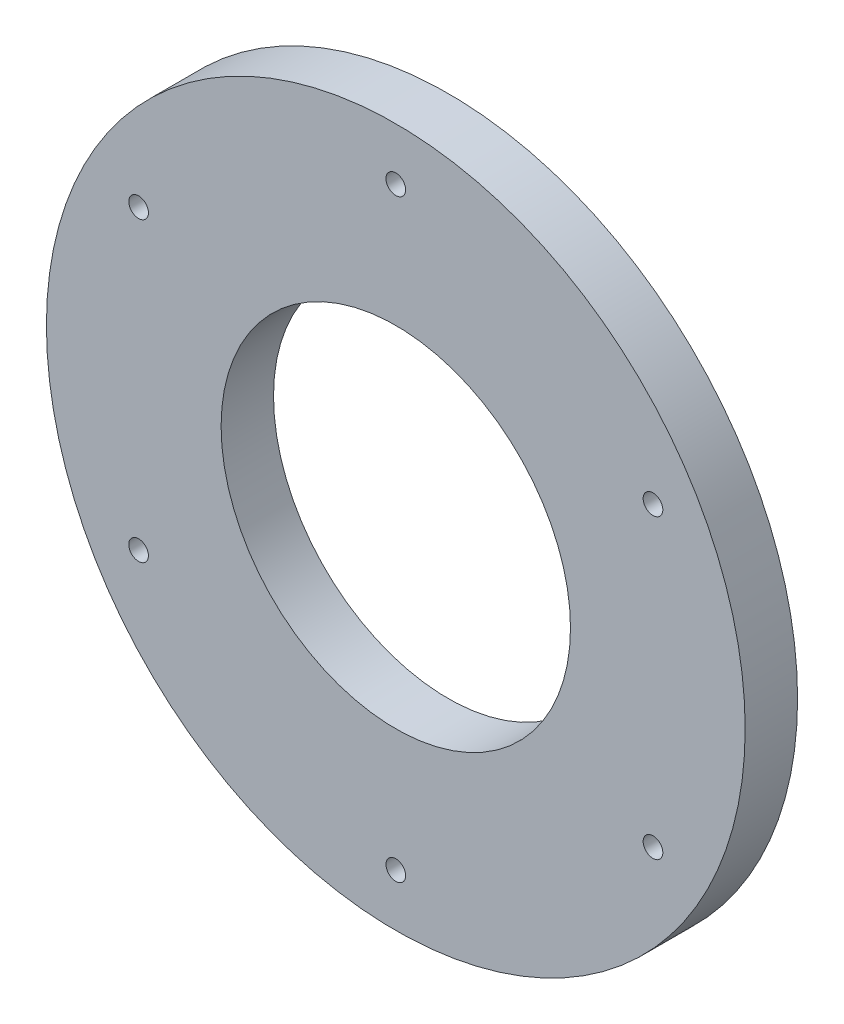
SolidWorks part; units mm, degrees
ref_plane "Front Plane" through (0, 0, 0) normal (0, 0, 1) x (1, 0, 0)
ref_plane "Top Plane" through (0, 0, 0) normal (0, 1, 0) x (1, 0, 0)
ref_plane "Right Plane" through (0, 0, 0) normal (1, 0, 0) x (0, 0, -1)
sketch "Sketch1" plane through (0, 0, 0) normal (0, 0, 1) x (1, 0, 0)
  circle A0 centre (0, 0) radius 127
  dimension "D1" = 254
extrude "Boss-Extrude1" add sketch "Sketch1" along normal blind 19.05
sketch "Sketch2" plane through (0, 0, 19.05) normal (0, 0, 1) x (1, 0, 0)
  circle A0 centre (0, 0) radius 107.95
  point P1 (0, 107.95)
  point P6 (93.4874, 53.975)
  point P9 (93.4874, -53.975)
  point P10 (0, -107.95)
  point P11 (-93.4874, -53.975)
  point P12 (-93.4874, 53.975)
  dimension "D1" = 215.9
  dimension "D2" = 6
hole_wizard "1/4 Clearance Hole1" positions "Sketch2" profile "Sketch3" hole size "1/4" standard "ANSI Inch" end condition up to next
sketch "Sketch3" plane through (-93.4874, 53.975, 19.05) normal (1, 0, 0) x (0, -1, 0)
  line L0 (0, 0) -> (0, 19.05)
  line L1 (0, 19.05) -> (3.5712, 19.05)
  line L2 (3.5712, 19.05) -> (3.5712, 0)
  line L5 (3.5712, 0) -> (0, 0)
  line L11 (0, -6.35) -> (0, 107.95) construction
  dimension "Thru Hole Dia." = 7.1425
  dimension "Thru Hole Depth" = 19.05
sketch "Sketch4" plane through (0, 0, 19.05) normal (0, 0, 1) x (1, 0, 0)
  circle A0 centre (0, 0) radius 63.5
  dimension "D1" = 127
extrude "Cut-Extrude1" cut sketch "Sketch4" against normal up to next
